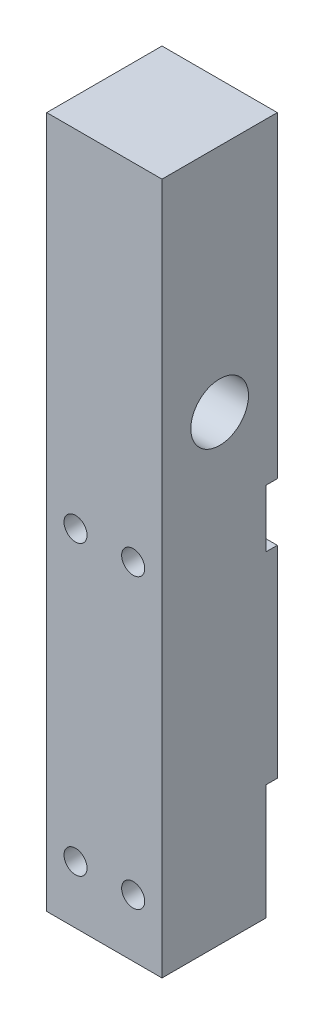
SolidWorks part; units mm, degrees
ref_plane "Front Plane" through (0, 0, 0) normal (0, 0, 1) x (1, 0, 0)
ref_plane "Top Plane" through (0, 0, 0) normal (0, 1, 0) x (1, 0, 0)
ref_plane "Right Plane" through (0, 0, 0) normal (1, 0, 0) x (0, 0, -1)
sketch "Sketch1" plane through (0, 0, 0) normal (1, 0, 0) x (0, 0, -1)
  line L0 (0, 55) -> (0, -55) construction
  line L1 (0, 120) -> (20, 120)
  line L2 (0, 120) -> (0, 0)
  line L3 (0, 0) -> (20, 0)
  line L4 (20, 120) -> (20, 0)
  line L5 (55, 0) -> (-55, 0) construction
  circle A2 centre (10, 80) radius 2.5
  dimension "D3" = 5
  dimension "D4" = 40
  dimension "D5" = 10
  dimension "D1" = 20
  dimension "D2" = 120
extrude "Boss-Extrude2" add sketch "Sketch1" against normal blind 20
ref_plane "Plane1" through (0, 0, 0) normal (1, 0, 0) x (0, 0, -1)
sketch "Sketch10" plane through (0, 0, 0) normal (1, 0, 0) x (0, 0, -1)
  circle A0 centre (10, 80) radius 5
  dimension "D1" = 10
extrude "Cut-Extrude1" cut sketch "Sketch10" against normal blind 10
ref_plane "Plane2" through (0, 0, 0) normal (0, 0, 1) x (1, 0, 0)
sketch "Sketch11" plane through (0, 0, 0) normal (0, 0, 1) x (1, 0, 0)
  line L0 (-10, 120) -> (-10, 0)
  line L1 (-20, 120) -> (0, 120) construction
  line L2 (11, 0) -> (-11, 0) construction
  line L3 (-20, 120) -> (-20, 0) construction
  line L4 (-20, 0) -> (0, 0) construction
  circle A0 centre (-15, 10) radius 1
  circle A1 centre (-5, 10) radius 1
  circle A2 centre (-15, 60) radius 1
  circle A3 centre (-5, 60) radius 1
  dimension "D1" = 2
  dimension "D4" = 2
  dimension "D2" = 5
  dimension "D3" = 10
  dimension "D5" = 60
extrude "Cut-Extrude2" cut sketch "Sketch11" against normal through all contours A0 | A1 | A0 region at (-15, 10, 0) region at (-5, 10, 0)
ref_plane "Plane3" through (0, 0, 0) normal (0, 0, 1) x (1, 0, 0)
sketch "Sketch12" plane through (0, 0, 0) normal (0, 0, 1) x (1, 0, 0)
  line L0 (11, 0) -> (-11, 0) construction
  circle A0 centre (-15, 10) radius 2
  circle A1 centre (-5, 10) radius 2
  circle A2 centre (-15, 60) radius 2
  circle A3 centre (-5, 60) radius 2
  dimension "D1" = 4
  dimension "D2" = 4
  dimension "D3" = 4
  dimension "D4" = 4
  dimension "D5" = 60
  dimension "D6" = 60
extrude "Cut-Extrude3" cut sketch "Sketch12" against normal blind 5
extrude "Cut-Extrude4" cut sketch "Sketch11<3>" against normal through all contours A2 | A3
sketch "Sketch11<3>" plane through (0, 0, 0) normal (0, 0, 1) x (1, 0, 0) same geometry as "Sketch11"
ref_plane "Plane4" through (0, 0, -20) normal (0, 0, -1) x (-1, 0, 0)
sketch "Sketch14" plane through (0, 0, -20) normal (0, 0, -1) x (-1, 0, 0)
  line L0 (11, 0) -> (-11, 0) construction
  line L1 (0, 65) -> (20, 65)
  line L2 (0, 65) -> (0, 55)
  line L3 (0, 55) -> (20, 55)
  line L4 (20, 65) -> (20, 55)
  line L5 (0, 65) -> (20, 55) construction
  line L6 (0, 55) -> (20, 65) construction
  line L7 (0, 20) -> (20, 20)
  line L8 (0, 20) -> (0, 0)
  line L9 (0, 0) -> (20, 0)
  line L10 (20, 20) -> (20, 0)
  line L11 (0, 20) -> (20, 0) construction
  line L12 (0, 0) -> (20, 20) construction
  line L13 (20, 0) -> (20, 120) construction
  point P0 (10, 60)
  point P5 (10, 10)
  dimension "D1" = 60
  dimension "D2" = 10
  dimension "D3" = 20
  dimension "D4" = 10
  dimension "D5" = 20
  dimension "D6" = 20
  dimension "D7" = 10
  dimension "D8" = 10
extrude "Cut-Extrude6" cut sketch "Sketch14" against normal blind 2
